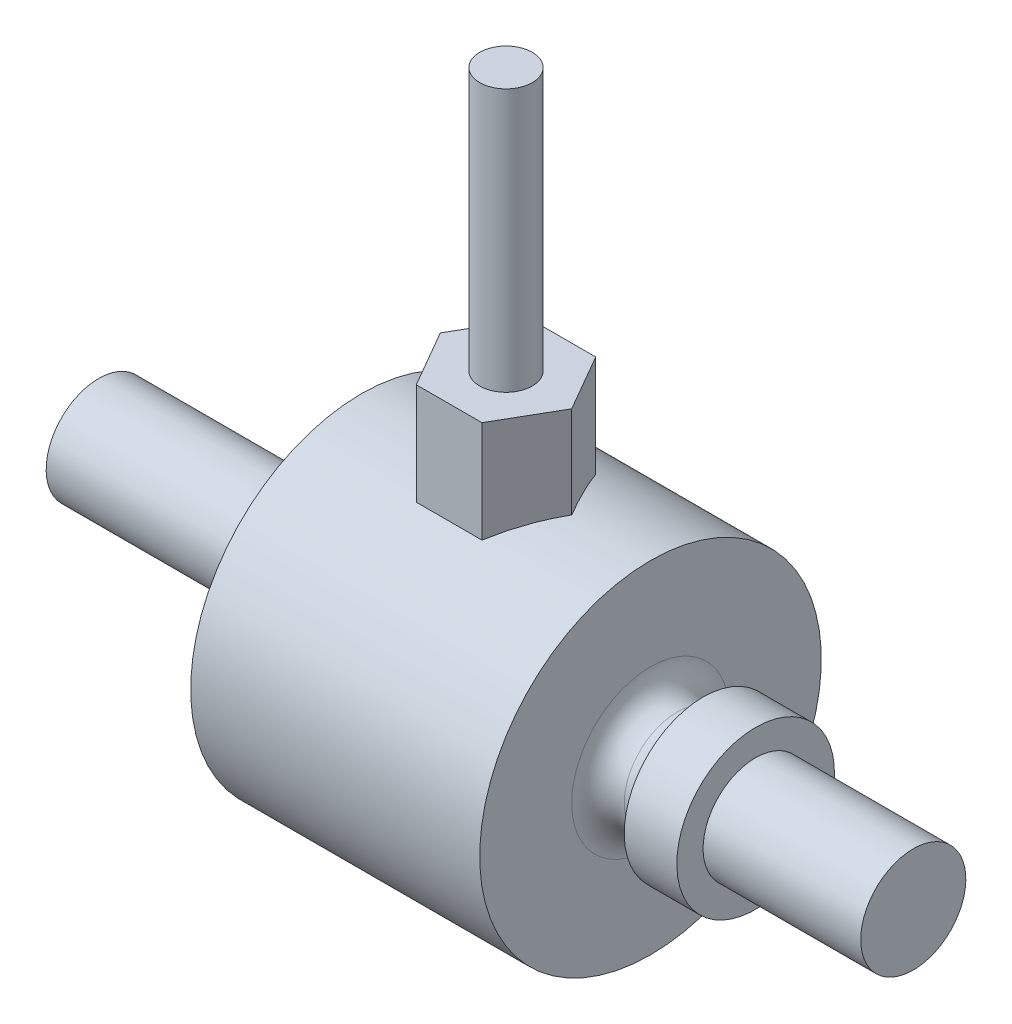
SolidWorks part; units mm, degrees
ref_plane "Front Plane" through (0, 0, 0) normal (0, 0, 1) x (1, 0, 0)
ref_plane "Top Plane" through (0, 0, 0) normal (0, 1, 0) x (1, 0, 0)
ref_plane "Right Plane" through (0, 0, 0) normal (1, 0, 0) x (0, 0, -1)
sketch "Sketch2" plane through (0, 0, 0) normal (0, 0, 1) x (1, 0, 0)
  line L0 (0, 0) -> (0, 2)
  line L1 (0, 2) -> (8, 2)
  line L2 (8, 2) -> (8, 3)
  line L3 (8, 3) -> (10, 3)
  line L4 (10, 3) -> (10, 6.5)
  line L5 (10, 6.5) -> (21, 6.5)
  line L6 (21, 6.5) -> (21, 2)
  line L7 (21, 2) -> (23, 2)
  line L8 (23, 2) -> (23, 3)
  line L9 (23, 3) -> (25, 3)
  line L10 (25, 3) -> (25, 2)
  line L11 (25, 2) -> (31, 2)
  line L12 (31, 2) -> (31, 0)
  line L13 (31, 0) -> (0, 0)
  point P4 (28, 2)
  point P16 (8, 2.5)
  point P17 (31, 1)
  point P18 (0, 1)
  dimension "D1" = 2
  dimension "D2" = 3
  dimension "D3" = 2
  dimension "D4" = 3
  dimension "D5" = 6.5
  dimension "D6" = 8
  dimension "D7" = 10
  dimension "D8" = 6
  dimension "D9" = 8
  dimension "D10" = 10
  dimension "D11" = 31
revolve "Revolve1" add sketch "Sketch2" angle 360 about L13
fillet "Fillet1" radius 1 2 edges at (23, 2, 0) (21, 2, 0)
sketch "Sketch3" plane through (0, 0, 0) normal (0, 1, 0) x (1, 0, 0)
  line L1 (16.75, 2.1651) -> (14.25, 2.1651)
  line L2 (14.25, 2.1651) -> (13, 0)
  line L3 (13, 0) -> (14.25, -2.1651)
  line L4 (14.25, -2.1651) -> (16.75, -2.1651)
  line L5 (16.75, -2.1651) -> (18, 0)
  line L6 (18, 0) -> (16.75, 2.1651)
  circle A0 centre (15.5, 0) radius 2.1651 construction
  dimension "D1" = 5
extrude "Boss-Extrude1" add sketch "Sketch3" along normal blind 10
sketch "Sketch4" plane through (0, 10, 0) normal (0, 1, 0) x (1, 0, 0)
  circle A0 centre (15.5, 0) radius 1
  dimension "D1" = 2
extrude "Boss-Extrude2" add sketch "Sketch4" along normal blind 10
